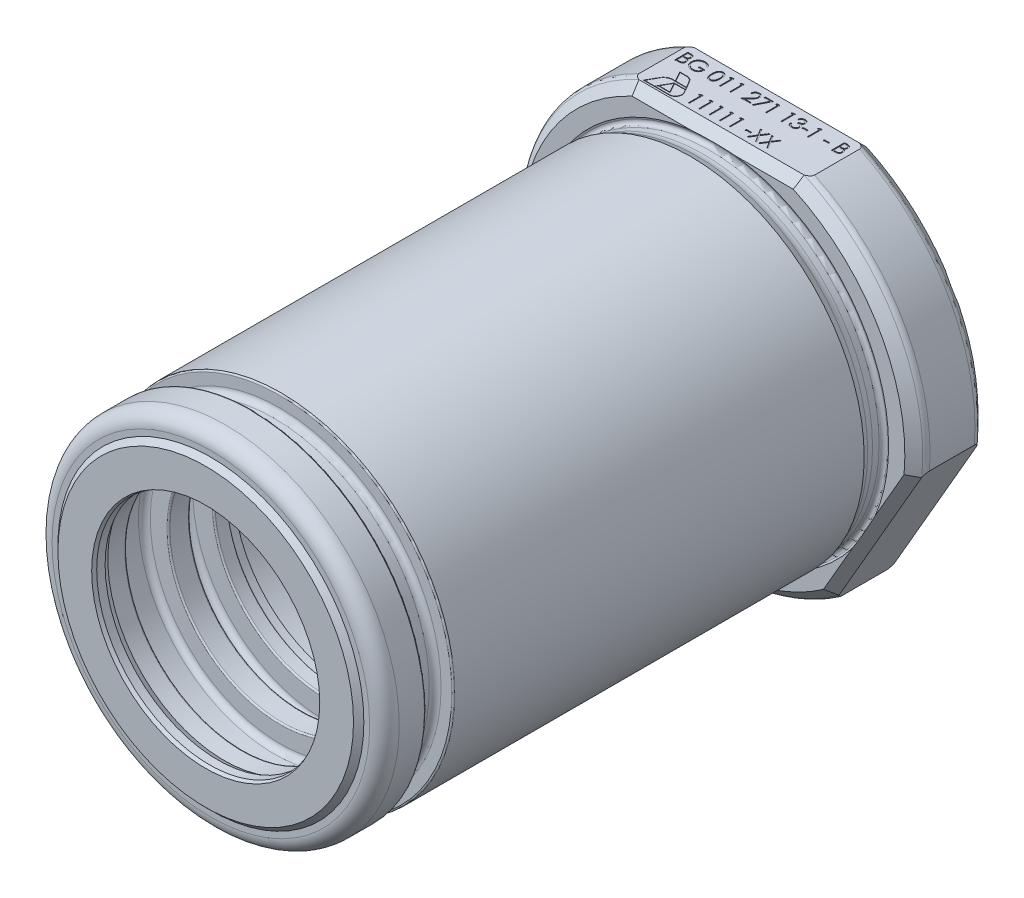
SolidWorks part; units mm, degrees
material "20MnV6"
ref_plane "Front Plane" through (0, 0, 0) normal (0, 0, 1) x (1, 0, 0)
ref_plane "Top Plane" through (0, 0, 0) normal (0, 1, 0) x (1, 0, 0)
ref_plane "Right Plane" through (0, 0, 0) normal (1, 0, 0) x (0, 0, -1)
sketch "Sketch1" plane through (0, 0, 0) normal (1, 0, 0) x (0, 0, -1)
  line L0 (29.906, -18.6002) -> (29.906, 18.3998) construction
  line L1 (0, 0) -> (82.7707, 0) construction
  line L2 (0.5, 15.25) -> (0, 15.432)
  line L3 (0.5, 15.25) -> (1.634, 15.25)
  line L4 (1.634, 15.25) -> (2.5, 15.75)
  line L5 (2.5, 15.75) -> (4.8, 15.75)
  line L6 (5, 15.95) -> (5, 17.6)
  line L7 (5.8, 18.4) -> (9.3, 18.4)
  line L8 (10.1, 17.6) -> (10.1, 15.35)
  line L9 (10.3, 15.15) -> (12.8, 15.15)
  line L10 (16.4, 15.15) -> (18, 15.15)
  line L11 (18, 15.15) -> (18, 15.25)
  line L12 (18.5, 15.75) -> (19.5, 15.75)
  line L13 (19.5, 15.75) -> (19.5, 17.494)
  line L14 (19.5, 17.494) -> (19.349, 18.0574)
  line L15 (20.3, 18.494) -> (20.082, 18.6199)
  line L16 (20.3, 18.494) -> (52.5, 18.494)
  line L17 (52.5, 18.494) -> (53.4554, 18.75)
  line L18 (53.4554, 18.75) -> (59.4304, 18.75)
  line L19 (61.5201, 19.6799) -> (61.4103, 19.5701)
  line L20 (63.5, 20.5) -> (77.3, 20.5)
  line L21 (77.3, 20.5) -> (78.5, 21.0596)
  line L22 (78.5, 26) -> (78.5, 21.0596)
  line L23 (70.5142, 27.5) -> (76.5858, 27.5)
  line L24 (77.2929, 27.2071) -> (78.5, 26)
  line L25 (0, 15.432) -> (0, 20)
  line L26 (0, 20) -> (0.7, 20.7)
  line L27 (0.7, 20.7) -> (0.7, 21.485)
  line L28 (6.1, 23.485) -> (2.7, 23.485)
  line L29 (10.2, 23.5) -> (65.6, 23.5)
  line L30 (65.6, 23.5) -> (66.4849, 23.0874)
  line L31 (67.3301, 22.9) -> (68.2135, 22.9)
  line L32 (13, 15.35) -> (13, 17.95)
  line L33 (68.6, 23.8) -> (68.6, 26)
  line L34 (13.8, 18.75) -> (15.4, 18.75)
  line L35 (16.2, 17.95) -> (16.2, 15.35)
  line L36 (29.3542, -18.8842) -> (29.3542, 18.1158) construction
  line L38 (6.3, 23.285) -> (6.3, 21.85)
  line L39 (7.1, 21.05) -> (9.2, 21.05)
  line L40 (10, 23.3) -> (10, 21.85)
  line L41 (69.8071, 27.2071) -> (68.6, 26)
  line L42 (68.6, 23.8) -> (68.6833, 23.571)
  arc A0 (59.4304, 18.75) -> (61.4103, 19.5701) centre (59.4304, 21.55) ccw
  arc A1 (61.5201, 19.6799) -> (63.5, 20.5) centre (63.5, 17.7) cw
  arc A2 (68.6833, 23.571) -> (68.2135, 22.9) centre (68.2135, 23.4) cw
  arc A3 (20.082, 18.6199) -> (19.349, 18.0574) centre (19.832, 18.1869) ccw
  arc A4 (0.7, 21.485) -> (2.7, 23.485) centre (2.7, 21.485) cw
  arc A5 (9.3, 18.4) -> (10.1, 17.6) centre (9.3, 17.6) cw
  arc A6 (5, 17.6) -> (5.8, 18.4) centre (5.8, 17.6) cw
  arc A7 (15.4, 18.75) -> (16.2, 17.95) centre (15.4, 17.95) cw
  arc A8 (13, 17.95) -> (13.8, 18.75) centre (13.8, 17.95) cw
  arc A9 (9.2, 21.05) -> (10, 21.85) centre (9.2, 21.85) ccw
  arc A10 (6.3, 21.85) -> (7.1, 21.05) centre (7.1, 21.85) ccw
  arc A11 (4.8, 15.75) -> (5, 15.95) centre (4.8, 15.95) ccw
  arc A12 (10.1, 15.35) -> (10.3, 15.15) centre (10.3, 15.35) ccw
  arc A13 (12.8, 15.15) -> (13, 15.35) centre (12.8, 15.35) ccw
  arc A14 (16.4, 15.15) -> (16.2, 15.35) centre (16.4, 15.35) cw
  arc A15 (6.1, 23.485) -> (6.3, 23.285) centre (6.1, 23.285) cw
  arc A16 (10.2, 23.5) -> (10, 23.3) centre (10.2, 23.3) ccw
  arc A17 (76.5858, 27.5) -> (77.2929, 27.2071) centre (76.5858, 26.5) cw
  arc A19 (18, 15.25) -> (18.5, 15.75) centre (18.5, 15.25) cw
  arc A20 (69.8071, 27.2071) -> (70.5142, 27.5) centre (70.5142, 26.5) cw
  arc A21 (67.3301, 22.9) -> (66.4849, 23.0874) centre (67.3301, 24.9) cw
  point P7 (48.5788, -0.0484)
  point P71 (13, 15.15)
  dimension "D2" = 55
  dimension "D20" = 15
  dimension "D21" = 2.8
  dimension "D22" = 2.8
  dimension "D23" = 0.5
  dimension "D30" = 0.5
  dimension "D44" = 2
  dimension "D51" = 0.8
  dimension "D52" = 0.8
  dimension "D53" = 0.8
  dimension "D54" = 0.2
  dimension "D55" = 0.2
  dimension "D56" = 1
  dimension "D57" = 1
  dimension "D58" = 0.5
  dimension "D64" = 2
  dimension "D1" = 37
  dimension "D3" = 41
  dimension "D4" = 40
  dimension "D5" = 45
  dimension "D6" = 0.7
  dimension "D7" = 46.97
  dimension "D8" = 25
  dimension "D9" = 45.8
  dimension "D10" = 47
  dimension "D11" = 9.9
  dimension "D12" = 36.988
  dimension "D13" = 78.5
  dimension "D14" = 37.5
  dimension "D15" = 52
  dimension "D16" = 45
  dimension "D17" = 15
  dimension "D18" = 26
  dimension "D19" = 45
  dimension "D24" = 3
  dimension "D25" = 1.2
  dimension "D26" = 25
  dimension "D27" = 59
  dimension "D28" = 1
  dimension "D29" = 0.8
  dimension "D31" = 30
  dimension "D32" = 1.5
  dimension "D33" = 30.3
  dimension "D34" = 3.2
  dimension "D35" = 65.5
  dimension "D36" = 73.5
  dimension "D37" = 5.1
  dimension "D38" = 36.8
  dimension "D39" = 37.5
  dimension "D40" = 31.5
  dimension "D41" = 76
  dimension "D42" = 30
  dimension "D43" = 30.5
  dimension "D45" = 68.5
  dimension "D46" = 3.7
  dimension "D47" = 42.1
  dimension "D48" = 31.5
  dimension "D49" = 20
  dimension "D50" = 0.5
  dimension "D59" = 37
  dimension "D60" = 77.8
  dimension "D61" = 45
  dimension "D62" = 20
  dimension "D63" = 0.3
  dimension "D65" = 52
revolve "Revolve1" add sketch "Sketch1" angle 360 about L1
sketch "Sketch3" plane through (0, 0, -78.5) normal (0, 0, -1) x (-1, 0, 0)
  line L0 (0, 0) -> (0, 53.252) construction
  line L1 (-27.5272, 45.7731) -> (27.5272, 45.7731)
  line L2 (-27.5272, 45.7731) -> (-27.5272, 24.8)
  line L3 (-27.5272, 24.8) -> (27.5272, 24.8)
  line L4 (27.5272, 45.7731) -> (27.5272, 24.8)
  circle A0 centre (0, 0) radius 27.5 construction
  dimension "D4" = 52.3
  dimension "D1" = 24.8
  dimension "D2" = 20.9731
  dimension "D3" = 55.0543
extrude "FLAT Cut-Extrude1" cut sketch "Sketch3" against normal up to surface (9.9 mm away) up to face at (23.8, 0, -68.6)
pattern_circular "CirPattern1" count 3 over 360 about axis through (0, 0, 0) along (0, 0, 1) of "FLAT Cut-Extrude1"
sketch "Sketch2" plane through (-24.7, 24.8, 0) normal (0, -1, 0) x (0, 0, -1)
  line L0 (74.527, 12.8168) -> (74.527, 36.5832) construction
  line L1 (76.5858, 36.5832) -> (70.5142, 36.5832) construction
  line L2 (70.5142, 12.8168) -> (76.5858, 12.8168) construction
  text T0 "BG 011 271 13-1 - B\r\n11111 -XX" font "Century Gothic" height 1.8
  line B0 (70.0484, 17.3341) -> (70.0484, 15.373)
  line B1 (70.4481, 17.0436) -> (70.4481, 15.6003)
  line B2 (70.1084, 15.4071) -> (70.3881, 15.5662)
  line B3 (72.1149, 16.1278) -> (72.1149, 15.7858)
  line B4 (73.4733, 15.373) -> (72.1149, 16.1278)
  line B5 (70.4481, 17.0436) -> (71.7365, 16.3329)
  line B6 (71.7365, 17.9106) -> (71.4266, 18.0898)
  line B7 (73.4733, 16.3354) -> (73.4733, 15.373)
  line B8 (72.1149, 17.7042) -> (71.7365, 17.9106)
  line B9 (72.1149, 17.7042) -> (72.9888, 17.1859)
  line B10 (70.0484, 15.373) -> (70.0484, 13.8745)
  line B11 (71.5299, 14.717) -> (70.0484, 13.8745)
  line B12 (71.7967, 17.8232) -> (72.0549, 17.67)
  line B13 (73.4133, 16.3354) -> (73.4133, 15.475)
  line B14 (73.4133, 15.475) -> (72.1149, 16.1964)
  line B15 (72.0549, 15.7858) -> (72.0549, 17.67)
  line B16 (71.4988, 14.7684) -> (70.1084, 13.9777)
  line B17 (70.1084, 15.3381) -> (70.1084, 13.9777)
  line B18 (71.7967, 16.2981) -> (71.7967, 17.8232)
  line B19 (70.1084, 15.3381) -> (71.7967, 16.2981)
  line B20 (71.7365, 17.8412) -> (71.3955, 18.0386)
  line B21 (70.1084, 17.3341) -> (70.1084, 15.4071)
  line B22 (72.1149, 16.1964) -> (72.1149, 17.6344)
  line B23 (72.1149, 17.6344) -> (72.9582, 17.1343)
  line B24 (70.3881, 17.1452) -> (70.3881, 15.5662)
  line B25 (70.3881, 17.1452) -> (71.7365, 16.4014)
  line B26 (71.7365, 16.4014) -> (71.7365, 17.8412)
  line B27 (70.4481, 15.6003) -> (71.7365, 16.3329)
  arc B28 (72.9888, 17.1859) -> (73.4733, 16.3354) centre (72.4845, 16.3354) cw
  arc B29 (70.0484, 17.3341) -> (71.4266, 18.0898) centre (70.9447, 17.3341) cw
  arc B30 (72.1149, 15.7858) -> (71.5299, 14.717) centre (70.8461, 15.7858) cw
  arc B31 (72.9582, 17.1343) -> (73.4133, 16.3354) centre (72.4845, 16.3354) cw
  arc B32 (72.0549, 15.7858) -> (71.4988, 14.7684) centre (70.8461, 15.7858) cw
  arc B33 (70.1084, 17.3341) -> (71.3955, 18.0386) centre (70.9447, 17.3341) cw
sketch_block_instance "SKETCH LOGO-2"
sketch_block "SKETCH LOGO" parameters "D1"=29.059, "D2"=11.4163, "D3"=29.624, "D4"=6.8884
chamfer "Chamfer1" distance 1.2 angle 45 3 edges at (-21.4774, -12.4, -78.5) (21.4774, -12.4, -78.5) (0, 24.8, -78.5)
chamfer "Chamfer2" distance 1.2 angle 45 1 edges at (0, 24.8, -68.6)
chamfer "Chamfer3" distance 1.2 angle 45 1 edges at (21.4774, -12.4, -68.6)
chamfer "Chamfer4" distance 1.2 angle 45 1 edges at (-21.4774, -12.4, -68.6)
sketch "Sketch4" plane through (0, 0, 0) normal (0, 1, 0) x (1, 0, 0)
  line L0 (0, 0) -> (0, 88.8764) construction
  line L1 (-10.9105, 78.5) -> (10.9105, 78.5) construction
  circle A0 centre (0, 82.1) radius 4
  point P7 (-1.7436, 78.5)
  point P8 (1.7436, 78.5)
  dimension "D1" = 0.4
  dimension "D3" = 8
  dimension "D2" = 3.4871
extrude "FACE SLOT Cut-Extrude1" cut sketch "Sketch4" against normal through all
pattern_circular "CirPattern2" count 6 over 360 about axis through (0, 0, 0) along (0, 0, 1) of "FACE SLOT Cut-Extrude1"
extrude "PN Cut-Extrude2" cut sketch "Sketch2" along normal blind 0.1
